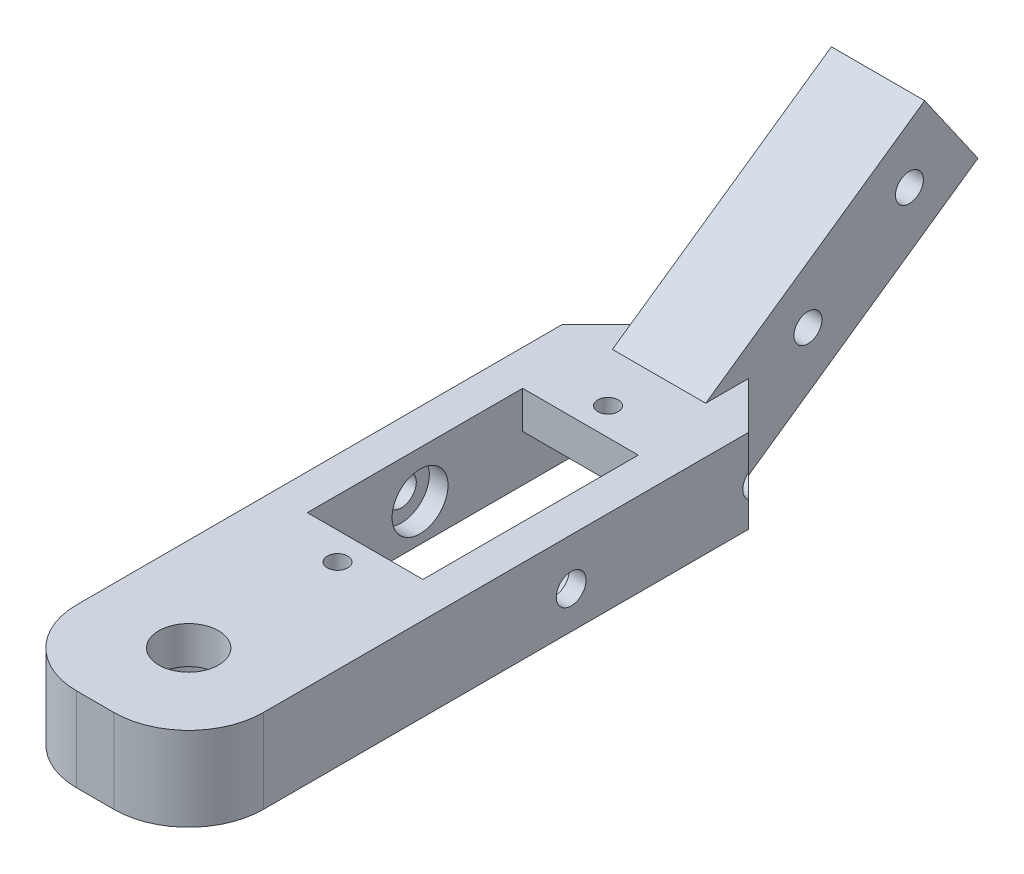
SolidWorks part; units mm, degrees
ref_plane "前视基准面" through (0, 0, 0) normal (0, 0, 1) x (1, 0, 0)
ref_plane "上视基准面" through (0, 0, 0) normal (0, 1, 0) x (1, 0, 0)
ref_plane "右视基准面" through (0, 0, 0) normal (1, 0, 0) x (0, 0, -1)
sketch "草图1" plane through (0, 0, 0) normal (1, 0, 0) x (0, 0, -1)
  line L1 (55, -4) -> (-10, -4)
  line L2 (55, -4) -> (55, 5)
  line L3 (55, 5) -> (-10, 5)
  line L4 (-10, -4) -> (-10, 5)
  line L5 (55, -4) -> (-10, 5) construction
  line L6 (55, 5) -> (-10, -4) construction
  point P0 (22.5, 0.5)
extrude "凸台-拉伸1" add sketch "草图1" along normal mid plane 20
sketch "草图2" plane through (0, -4, 0) normal (0, 1, 0) x (1, 0, 0)
  circle A0 centre (0, 0) radius 6.7
extrude "切除-拉伸1" cut sketch "草图2" along normal blind 5
sketch "草图4" plane through (0, 1, 0) normal (0, -1, 0) x (1, 0, 0)
  circle A0 centre (0, 0) radius 3.2
extrude "切除-拉伸3" cut sketch "草图4" against normal through all
sketch "草图3" plane through (0, 5, 0) normal (0, 1, 0) x (1, 0, 0)
  line L1 (6.2, 42) -> (-6.2, 42)
  line L2 (6.2, 42) -> (6.2, 18.9147)
  line L3 (6.2, 18.9147) -> (-6.2, 18.9147)
  line L4 (-6.2, 42) -> (-6.2, 18.9147)
  line L5 (6.2, 42) -> (-6.2, 18.9147) construction
  line L6 (6.2, 18.9147) -> (-6.2, 42) construction
  point P0 (0, 30.4574)
extrude "切除-拉伸2" cut sketch "草图3" against normal through all
sketch "草图5" plane through (0, -4, 0) normal (0, -1, 0) x (1, 0, 0)
  line L1 (6.2, -47.9147) -> (-6.2, -47.9147)
  line L2 (6.2, -47.9147) -> (6.2, -13)
  line L3 (6.2, -13) -> (-6.2, -13)
  line L4 (-6.2, -47.9147) -> (-6.2, -13)
  line L5 (6.2, -47.9147) -> (-6.2, -13) construction
  line L6 (6.2, -13) -> (-6.2, -47.9147) construction
  line L7 (-6.2, -42) -> (-6.2, -18.9147) construction
  line L8 (-6.2, -18.9147) -> (6.2, -18.9147) construction
  point P0 (0, -30.4574)
  point P8 (-6.2, -30.4574)
  point P11 (0, -18.9147)
extrude "切除-拉伸4" cut sketch "草图5" against normal offset from surface (5 mm away) 4 up to face at (0, 5, -30.4574)
sketch "草图6" plane through (0, 1, 0) normal (0, -1, 0) x (1, 0, 0)
  line L0 (-6.2, -30.4574) -> (6.2, -30.4574) construction
  line L1 (-6.2, -47.9147) -> (-6.2, -13) construction
  line L2 (6.2, -13) -> (6.2, -47.9147) construction
  line L3 (0, -30.4574) -> (0, -15.9574) construction
  circle A0 centre (0, -15.9574) radius 1.1
  circle A2 centre (0, -44.9574) radius 1.1
extrude "切除-拉伸5" cut sketch "草图6" against normal through all
fillet "圆角1" radius 8 2 edges at (-10, 0.5, 10) (10, 0.5, 10)
sketch "草图7" plane through (10, 0, 0) normal (1, 0, 0) x (0, 0, -1)
  line L0 (31.0016, 0) -> (51.0016, 0) construction
  circle A0 centre (51.0016, 0) radius 1.6
  circle A1 centre (31.0016, 0) radius 1.6
extrude "切除-拉伸6" cut sketch "草图7" against normal through all
sketch "草图8" plane through (-6.2, 0, 0) normal (1, 0, 0) x (0, 0, -1)
  circle A0 centre (31.0016, 0) radius 3
extrude "切除-拉伸7" cut sketch "草图8" against normal blind 2
mirror "镜向1" about plane through (0, 0, 0) normal (1, 0, 0) of "切除-拉伸7"
sketch "草图9" plane through (0, 0, 0) normal (1, 0, 0) x (0, 0, -1)
  line L0 (54.9927, -4.0051) -> (72.0635, 7.8882) construction
  line L1 (55, -4) -> (79.615, 13.1493)
  line L2 (79.615, 13.1493) -> (73.8986, 21.3544)
  line L3 (73.8986, 21.3544) -> (50.4246, 5)
  line L4 (55, 5) -> (-2, 5) construction
  line L5 (50.4246, 5) -> (55, 5)
  line L6 (55, 5) -> (55, -4)
  line L7 (76.7568, 17.2518) -> (55, 2.0938) construction
  circle A0 centre (72.2626, 14.1208) radius 1.5
  circle A1 centre (61.3838, 6.5414) radius 1.5
  point P1 (55, -4)
  point P6 (76.7568, 17.2518)
extrude "凸台-拉伸2" add sketch "草图9" along normal mid plane 10
chamfer "倒角1" distance 5 angle 45 2 edges at (-10, 0.5, -55) (10, 0.5, -55)
